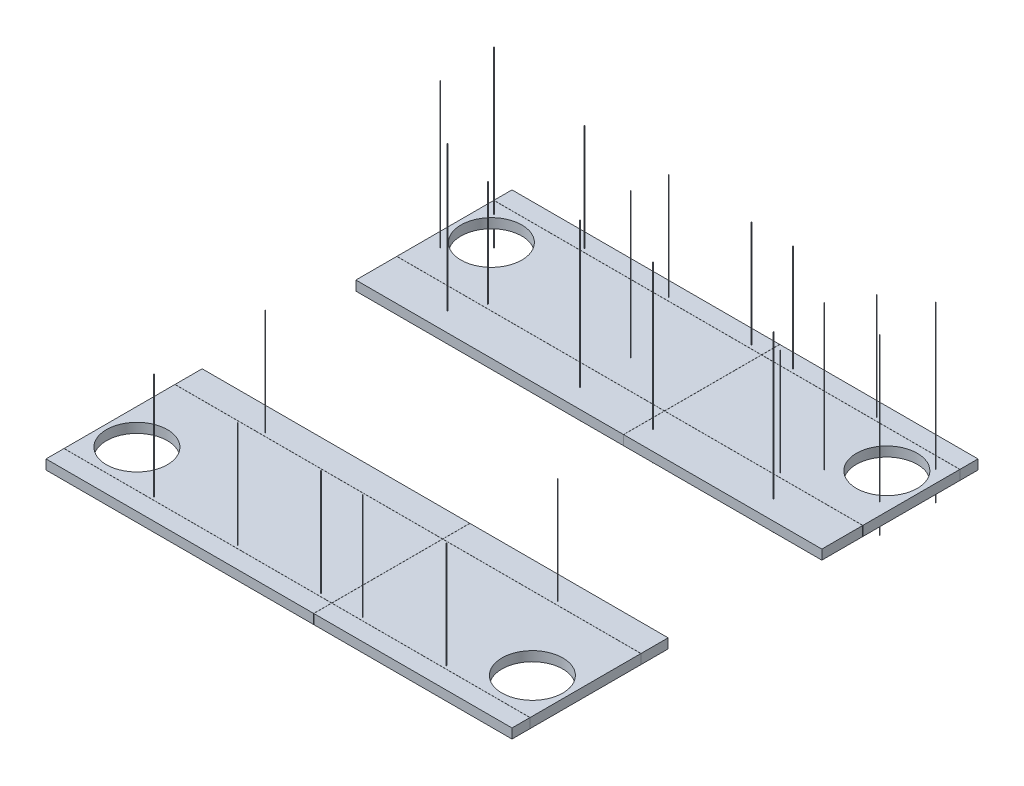
SolidWorks part; units mm, degrees
ref_plane "Front" through (0, 0, 0) normal (0, 0, 1) x (1, 0, 0)
ref_plane "Top" through (0, 0, 0) normal (0, 1, 0) x (1, 0, 0)
ref_plane "Right" through (0, 0, 0) normal (1, 0, 0) x (0, 0, -1)
sketch "Sketch1" plane through (0, 0, 0) normal (0, 1, 0) x (1, 0, 0)
  line L1 (-2454.275, 2454.275) -> (2454.275, 2454.275)
  line L2 (-2454.275, 2454.275) -> (-2454.275, -2454.275)
  line L3 (-2454.275, -2454.275) -> (2454.275, -2454.275)
  line L4 (2454.275, 2454.275) -> (2454.275, -2454.275)
  line L5 (-2454.275, 2454.275) -> (2454.275, -2454.275) construction
  line L6 (-2454.275, -2454.275) -> (2454.275, 2454.275) construction
  point P0 (0, 0)
  dimension "D1" = 4908.55
  dimension "D2" = 4908.55
extrude "Boss-Extrude1" add sketch "Sketch1" along normal blind 101.6
sketch "Sketch2" plane through (0, 101.6, 0) normal (0, 1, 0) x (1, 0, 0)
  line L0 (-2454.275, 2454.275) -> (-2454.275, -2454.275) construction
  line L1 (2454.275, -809.625) -> (-2454.275, -809.625)
  line L2 (2454.275, -809.625) -> (2454.275, 809.625)
  line L3 (2454.275, 809.625) -> (-2454.275, 809.625)
  line L4 (-2454.275, -809.625) -> (-2454.275, 809.625)
  line L5 (2454.275, -809.625) -> (-2454.275, 809.625) construction
  line L6 (2454.275, 809.625) -> (-2454.275, -809.625) construction
  point P0 (0, 0)
  dimension "D1" = 1619.25
extrude "Cut-Extrude1" cut sketch "Sketch2" against normal through all
sketch "Sketch4" plane through (0, 101.6, 0) normal (0, 1, 0) x (1, 0, 0)
  line L0 (-2454.275, -2263.775) -> (2454.275, -2263.775)
  line L3 (-2454.275, -2454.275) -> (2454.275, -2454.275) construction
  line L4 (-2454.275, -1095.375) -> (2454.275, -1095.375)
  line L5 (-2454.275, -809.625) -> (-2454.275, -2454.275) construction
  line L6 (-2454.275, -809.625) -> (2454.275, -809.625) construction
  line L7 (-2454.275, 2263.775) -> (2454.275, 2263.775)
  line L10 (-2454.275, 1241.425) -> (2454.275, 1241.425)
  line L11 (-2454.275, 2454.275) -> (-2454.275, 809.625) construction
  line L12 (2454.275, 809.625) -> (2454.275, 2454.275) construction
  line L13 (2454.275, 2454.275) -> (-2454.275, 2454.275) construction
  line L14 (2454.275, 809.625) -> (-2454.275, 809.625) construction
  line L15 (-2454.275, -1095.375) -> (-2454.275, -2263.775) construction
  line L16 (2454.275, -1095.375) -> (2454.275, -2263.775) construction
  line L17 (2454.275, 1241.425) -> (2454.275, 2263.775) construction
  line L18 (-2454.275, 1241.425) -> (-2454.275, 2263.775) construction
  line L19 (2454.275, -2454.275) -> (2454.275, -809.625) construction
  dimension "D1" = 190.5
  dimension "D2" = 1168.4
  dimension "D3" = 285.75
  dimension "D4" = 190.5
  dimension "D5" = 1022.35
  dimension "D6" = 431.8
extrude "Cut-Extrude-Thin1" cut sketch "Sketch4" against normal through all thin thin type one direction wall 1.27
sketch "Sketch5" plane through (0, 101.6, 0) normal (0, 1, 0) x (1, 0, 0)
  line L0 (365.125, -2454.275) -> (365.125, 2454.275)
  line L1 (-2454.275, -2454.275) -> (2454.275, -2454.275) construction
  line L2 (2454.275, 2454.275) -> (-2454.275, 2454.275) construction
  line L3 (2454.275, -2263.775) -> (2454.275, -1096.645) construction
  line L4 (-2454.275, -1096.645) -> (-2454.275, -2263.775) construction
  dimension "D1" = 2089.15
  dimension "D2" = 2819.4
extrude "Cut-Extrude-Thin2" cut sketch "Sketch5" against normal through all and the other way through all thin thin type one direction wall 1.27
sketch "Sketch3" plane through (0, 101.6, 0) normal (0, 1, 0) x (1, 0, 0)
  line L1 (-2276.475, -2263.775) -> (-1520.6938, -2263.775)
  line L2 (-2276.475, -2263.775) -> (-2276.475, -1507.9938)
  line L3 (-2276.475, -1507.9938) -> (-1520.6938, -1507.9938)
  line L4 (-1520.6938, -2263.775) -> (-1520.6938, -1507.9938)
  line L5 (2276.475, -2263.775) -> (1520.6938, -2263.775)
  line L6 (2276.475, -2263.775) -> (2276.475, -1507.9938)
  line L7 (2276.475, -1507.9938) -> (1520.6938, -1507.9938)
  line L8 (1520.6938, -2263.775) -> (1520.6938, -1507.9938)
  line L9 (-2276.475, 2263.775) -> (-1520.6938, 2263.775)
  line L10 (-2276.475, 2263.775) -> (-2276.475, 1507.9938)
  line L11 (-2276.475, 1507.9938) -> (-1520.6938, 1507.9938)
  line L12 (-1520.6938, 2263.775) -> (-1520.6938, 1507.9938)
  line L13 (2276.475, 2263.775) -> (1520.6938, 2263.775)
  line L14 (2276.475, 2263.775) -> (2276.475, 1507.9938)
  line L15 (2276.475, 1507.9938) -> (1520.6938, 1507.9938)
  line L16 (1520.6938, 2263.775) -> (1520.6938, 1507.9938)
  line L19 (2454.275, -2263.775) -> (2454.275, -1096.645) construction
  line L20 (366.395, -2263.775) -> (2454.275, -2263.775) construction
  line L21 (-2454.275, -2263.775) -> (365.125, -2263.775) construction
  line L22 (-2454.275, -1096.645) -> (-2454.275, -2263.775) construction
  line L23 (366.395, 2263.775) -> (2454.275, 2263.775) construction
  line L24 (2454.275, 1241.425) -> (2454.275, 2262.505) construction
  line L25 (-2454.275, 2262.505) -> (-2454.275, 1241.425) construction
  line L26 (-2454.275, 2263.775) -> (365.125, 2263.775) construction
  dimension "D1" = 177.8
  dimension "D2" = 177.8
  dimension "D3" = 177.8
  dimension "D4" = 177.8
extrude "SQUARE HOLE" [suppressed] cut sketch "Sketch3" against normal through all
sketch "Sketch6" plane through (0, 101.6, 0) normal (0, 1, 0) x (1, 0, 0)
  line L0 (2082.8, 1865.63) -> (2082.8, 2262.505) construction
  line L1 (-2082.8, 1865.63) -> (2082.8, 1865.63) construction
  line L2 (-2082.8, 1865.63) -> (-2082.8, -1868.17) construction
  line L3 (-2082.8, -1868.17) -> (2082.8, -1868.17) construction
  line L4 (2082.8, 1865.63) -> (2082.8, -1868.17) construction
  line L5 (-2082.8, -1868.17) -> (-2082.8, -2265.045) construction
  line L6 (-2454.275, -2265.045) -> (365.125, -2265.045) construction
  line L7 (366.395, 2262.505) -> (2454.275, 2262.505) construction
  line L9 (2454.275, 1241.425) -> (2454.275, 2262.505) construction
  line L11 (-2454.275, -1096.645) -> (-2454.275, -2263.775) construction
  circle A0 centre (2082.8, 1865.63) radius 320.675
  circle A1 centre (-2082.8, 1865.63) radius 320.675
  circle A2 centre (-2082.8, -1868.17) radius 320.675
  circle A3 centre (2082.8, -1868.17) radius 320.675
  dimension "D1" = 641.35
  dimension "D3" = 50.8
  dimension "D4" = 50.8
  dimension "D2" = 76.2
extrude "Cut-Extrude2" cut sketch "Sketch6" against normal through all
sketch "Sketch7" plane through (0, 101.6, 0) normal (0, 1, 0) x (1, 0, 0)
  line L0 (-1539.875, 2301.875) -> (-295.275, 2301.875) construction
  line L1 (-1539.875, 2301.875) -> (-2454.275, 2301.875) construction
  line L2 (-2454.275, 2454.275) -> (-2454.275, 2263.775) construction
  line L3 (365.125, 2454.275) -> (-2454.275, 2454.275) construction
  line L4 (-295.275, 2301.875) -> (365.125, 2301.875) construction
  line L5 (365.125, 2263.775) -> (365.125, 2454.275) construction
  line L6 (1743.075, 1546.225) -> (1743.075, 1012.825) construction
  line L7 (365.125, 2301.875) -> (974.725, 2301.875) construction
  line L8 (974.725, 2301.875) -> (1743.075, 2301.875) construction
  line L9 (1743.075, 2301.875) -> (2454.275, 2301.875) construction
  line L10 (2454.275, 2263.775) -> (2454.275, 2454.275) construction
  line L11 (366.395, 2263.775) -> (366.395, 2454.275) construction
  line L12 (2454.275, 1546.225) -> (-2454.275, 1546.225) construction
  line L13 (2454.275, 1241.425) -> (2454.275, 2262.505) construction
  line L14 (-2454.275, 2262.505) -> (-2454.275, 1241.425) construction
  line L15 (1743.075, 2301.875) -> (1743.075, 1546.225) construction
  line L16 (-2454.275, 1241.425) -> (365.125, 1241.425) construction
  line L17 (-295.275, 2301.875) -> (-295.275, 1546.225) construction
  line L18 (974.725, 2301.875) -> (974.725, 1546.225) construction
  line L19 (-2454.275, 2136.775) -> (2454.275, 2136.775) construction
  line L20 (-2454.275, 2263.775) -> (365.125, 2263.775) construction
  line L21 (-1539.875, 2301.875) -> (-1539.875, 2136.775) construction
  line L22 (-2454.275, 1012.825) -> (2454.275, 1012.825) construction
  line L23 (-2454.275, 1240.155) -> (-2454.275, 809.625) construction
  line L24 (2454.275, 809.625) -> (2454.275, 1240.155) construction
  line L25 (365.125, 809.625) -> (-2454.275, 809.625) construction
  line L26 (-1692.275, 1012.825) -> (-1692.275, 1546.225) construction
  line L27 (-295.275, 1546.225) -> (-295.275, 1012.825) construction
  line L28 (-2107.4102, -2022.1425) -> (-2107.4102, -819.4758) construction
  line L29 (-1539.875, 1285.875) -> (1539.875, 1285.875) construction
  circle A0 centre (-1539.875, 2301.875) radius 3.175
  circle A4 centre (1743.075, 1546.225) radius 3.175
  circle A5 centre (-1692.275, 1546.225) radius 3.175 construction
  circle A6 centre (473.075, 1012.825) radius 3.175
  circle A7 centre (-295.275, 1546.225) radius 3.175
  circle A8 centre (974.725, 1546.225) radius 3.175 construction
  circle A9 centre (-295.275, 2136.775) radius 3.175 construction
  circle A10 centre (-1539.875, 2136.775) radius 3.175 construction
  circle A11 centre (974.725, 2136.775) radius 3.175 construction
  circle A12 centre (1743.075, 2136.775) radius 3.175 construction
  circle A13 centre (-295.275, 1012.825) radius 3.175
  circle A14 centre (-1692.275, 1012.825) radius 3.175
  circle A15 centre (1743.075, 1012.825) radius 3.175
  circle A16 centre (-2301.875, 1546.225) radius 3.175
  circle A17 centre (2327.275, 1546.225) radius 3.175
  circle A18 centre (-2327.275, 2136.775) radius 3.175
  circle A19 centre (2327.275, 2136.775) radius 3.175
  circle A20 centre (219.075, 2301.875) radius 3.175
  circle A21 centre (658.495, 2301.875) radius 3.175
  circle A22 centre (1539.875, 2301.875) radius 3.175
  circle A23 centre (-650.875, 2301.875) radius 3.175
  circle A24 centre (-1539.875, 1285.875) radius 3.175
  circle A25 centre (1539.875, 1285.875) radius 3.175
  circle A26 centre (-1539.875, -1058.596) radius 3.175
  circle A27 centre (-1539.875, -2230.2499) radius 3.175
  circle A28 centre (-658.766, -2230.2499) radius 3.175
  circle A29 centre (219.075, -2230.2499) radius 3.175
  circle A30 centre (658.495, -2230.2499) radius 3.175
  circle A31 centre (1539.875, -2230.2499) radius 3.175
  circle A32 centre (1539.875, -1058.596) radius 3.175
  dimension "D1" = 6.35
  dimension "D5" = 609.6
  dimension "D7" = 304.8
  dimension "D11" = 127
  dimension "D14" = 152.4
  dimension "D19" = 889
  dimension "D20" = 914.4
  dimension "D21" = 1168.4
  dimension "D2" = 152.4
  dimension "D3" = 914.4
  dimension "D4" = 660.4
  dimension "D6" = 711.2
  dimension "D8" = 762
  dimension "D9" = 127
  dimension "D10" = 127
  dimension "D12" = 203.2
  dimension "D13" = 1981.2
  dimension "D15" = 127
  dimension "D16" = 146.05
  dimension "D17" = 292.1
  dimension "D18" = 914.4
  dimension "D22" = 3079.75
extrude "STUD LAYOUT SKETCH" add sketch "Sketch7" along normal blind 1524 and the other way blind 304.8 separate body
sketch "Sketch8" plane through (0, 1625.6, 0) normal (0, 1, 0) x (1, 0, 0)
  line L1 (-2748.8936, 3759.21) -> (2748.8936, 3759.21)
  line L2 (-2748.8936, 3759.21) -> (-2748.8936, -3759.21)
  line L3 (-2748.8936, -3759.21) -> (2748.8936, -3759.21)
  line L4 (2748.8936, 3759.21) -> (2748.8936, -3759.21)
  line L5 (-2748.8936, 3759.21) -> (2748.8936, -3759.21) construction
  line L6 (-2748.8936, -3759.21) -> (2748.8936, 3759.21) construction
  point P0 (0, 0)
  dimension "D1" = 7518.42
  dimension "D2" = 5497.7872
sketch "Sketch9" plane through (0, -203.2, 0) normal (0, -1, 0) x (1, 0, 0)
  line L1 (2592.4344, 3685.246) -> (-2592.4344, 3685.246)
  line L2 (2592.4344, 3685.246) -> (2592.4344, -3685.246)
  line L3 (2592.4344, -3685.246) -> (-2592.4344, -3685.246)
  line L4 (-2592.4344, 3685.246) -> (-2592.4344, -3685.246)
  line L5 (2592.4344, 3685.246) -> (-2592.4344, -3685.246) construction
  line L6 (2592.4344, -3685.246) -> (-2592.4344, 3685.246) construction
  point P0 (0, 0)
  dimension "D1" = 7370.492
  dimension "D2" = 5184.8688
extrude "Cut-Extrude5" cut sketch "Sketch8" against normal blind 406.4
extrude "Cut-Extrude6" cut sketch "Sketch9" against normal blind 254
